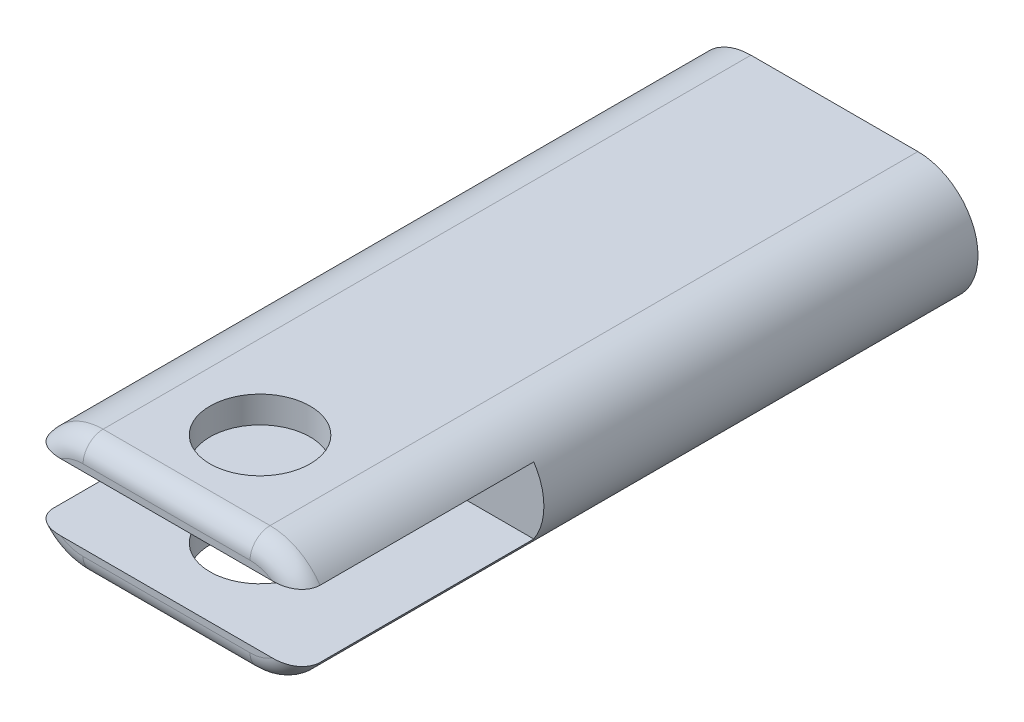
SolidWorks part; units mm, degrees
ref_plane "Front Plane" through (0, 0, 0) normal (0, 0, 1) x (1, 0, 0)
ref_plane "Top Plane" through (0, 0, 0) normal (0, 1, 0) x (1, 0, 0)
ref_plane "Right Plane" through (0, 0, 0) normal (1, 0, 0) x (0, 0, -1)
sketch "Sketch1" plane through (0, 0, 0) normal (0, 0, 1) x (1, 0, 0)
  line L0 (-125, 0) -> (125, 0) construction
  line L1 (-125, 90) -> (125, 90)
  line L2 (-125, -90) -> (125, -90)
  arc A0 (-125, 90) -> (-125, -90) centre (-125, 0) ccw
  arc A1 (125, -90) -> (125, 90) centre (125, 0) ccw
  point P3 (0, 0)
  dimension "D2" = 90
  dimension "D1" = 250
extrude "Boss-Extrude1" add sketch "Sketch1" along normal blind 1000
sketch "Sketch2" plane through (0, 0, 1000) normal (0, 0, 1) x (1, 0, 0)
  line L0 (0, -50) -> (0, 50) construction
  line L10 (215.603, 50) -> (-215.7854, 50)
  line L11 (215.603, 50) -> (215.603, -50)
  line L12 (215.603, -50) -> (-215.7854, -50)
  line L13 (-215.7854, 50) -> (-215.7854, -50)
  point P3 (0, 0)
  dimension "D1" = 100
fillet "Fillet1" radius 30 4 edges at (-215, 0, 1000) (215, 0, 1000) (0, 90, 1000) (0, -90, 1000)
extrude "Cut-Extrude1" cut sketch "Sketch2" against normal blind 350
sketch "Sketch3" plane through (0, 90, 0) normal (0, 1, 0) x (1, 0, 0)
  line L0 (125, -1000) -> (-125, -1000) construction
  circle A0 centre (0, -860) radius 75
  dimension "D1" = 150
  dimension "D2" = 140
extrude "Cut-Extrude2" cut sketch "Sketch3" against normal through all
